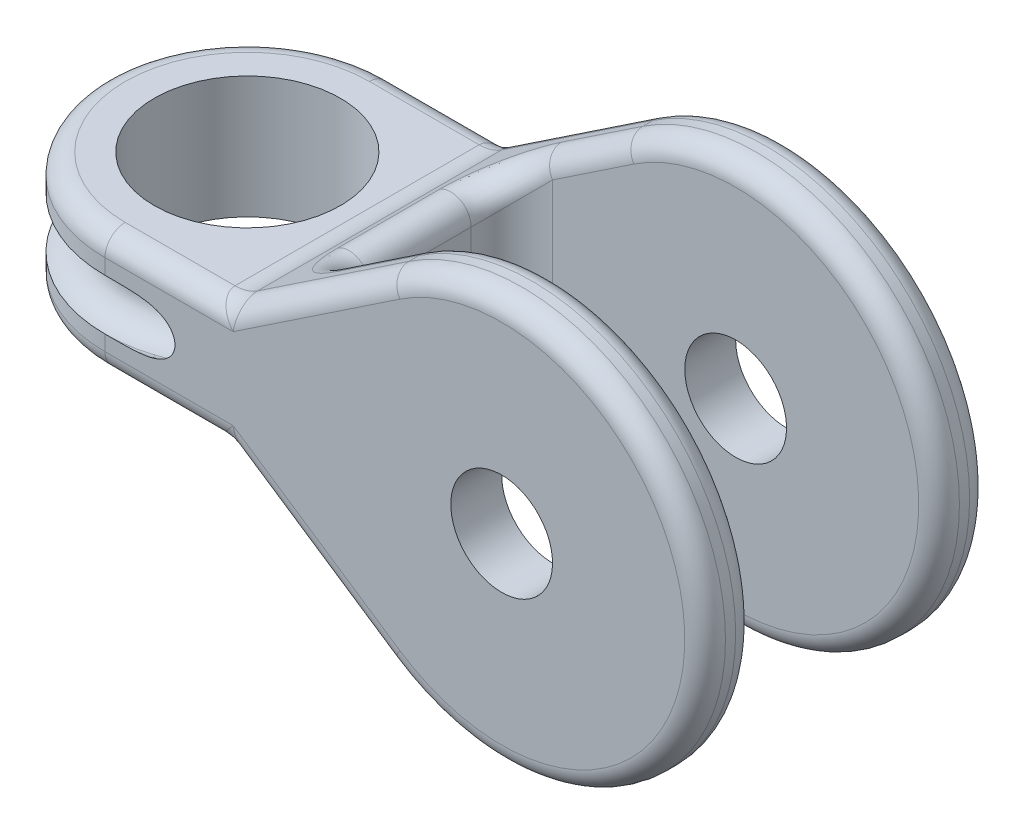
SolidWorks part; units mm, degrees
ref_plane "Front Plane" through (0, 0, 0) normal (0, 0, 1) x (1, 0, 0)
ref_plane "Top Plane" through (0, 0, 0) normal (0, 1, 0) x (1, 0, 0)
ref_plane "Right Plane" through (0, 0, 0) normal (1, 0, 0) x (0, 0, -1)
ref_plane "Front" through (0, 0, 4.5) normal (0, 0, 1) x (1, 0, 0)
ref_plane "Back" through (0, 0, -4.5) normal (0, 0, -1) x (-1, 0, 0)
sketch "Sketch8" plane through (0, 0, 4.5) normal (0, 0, 1) x (1, 0, 0)
  circle A0 centre (0, 0) radius 10
  circle A1 centre (0, 0) radius 2.5
  dimension "D1" = 20
  dimension "D2" = 5
extrude "Boss-Extrude3" add sketch "Sketch8" along normal blind 2.5
sketch "Sketch10" plane through (0, 0, -4.5) normal (0, 0, -1) x (-1, 0, 0)
  circle A0 centre (0, 0) radius 10
  circle A1 centre (0, 0) radius 2.5
  dimension "D1" = 20
  dimension "D2" = 5
extrude "Boss-Extrude4" add sketch "Sketch10" along normal blind 2.5 separate body
sketch "Sketch11" plane through (0, 0, 0) normal (0, 1, 0) x (1, 0, 0)
  line L0 (-38.7738, 0) -> (13.2618, 0) construction
  line L1 (-10, 7) -> (-10, -7) construction
  line L2 (-19.5, -7) -> (-13.5, -7)
  line L4 (-19.5, 7) -> (-13.5, 7)
  line L5 (-13.5, -7) -> (-13.5, 7)
  line L6 (-24.0555, -5.3148) -> (-13.5, 7) construction
  line L7 (-24.0555, 5.3148) -> (-13.5, -7) construction
  line L8 (-10, -7) -> (10, -7) construction
  arc A0 (-19.5, 7) -> (-19.5, -7) centre (-19.5, 0) ccw
  circle A1 centre (-19.5, 0) radius 4.575
  point P17 (-19.5, 0)
  dimension "D1" = 14
  dimension "D2" = 9.15
  dimension "D3" = 3.5
extrude "Boss-Extrude9" add sketch "Sketch11" along normal blind 3 and the other way blind 3 separate body contours L4 L5 L2 A0 | A1
sketch "Sketch12" plane through (0, 0, 0) normal (0, 1, 0) x (1, 0, 0)
  line L0 (-13.5, -7) -> (-10, -7)
  line L1 (-10, -7) -> (-10, 0)
  line L2 (-11, 0) -> (11, 0) construction
  line L3 (-10, 0) -> (-13.5, 0)
  line L4 (-13.5, -7) -> (-13.5, 7) construction
  line L5 (-13.5, 0) -> (-13.5, -7)
  point P0 (-13.5, -7)
  point P1 (-10, -7)
extrude "Boss-Extrude10" add sketch "Sketch12" along normal blind 3 and the other way blind 3
sketch "Sketch22" plane through (0, 0, 7) normal (0, 0, 1) x (1, 0, 0)
  line L0 (-19.5, 3) -> (-10, 3) construction
  line L1 (-10, 0) -> (-14.8775, 0) construction
  line L2 (-10, -3) -> (-10, 3) construction
  line L3 (-13.5, 3) -> (-5.5604, 8.3116)
  line L4 (-13.5, -3) -> (-5.5604, -8.3116)
  line L5 (-13.5, 3) -> (-13.5, -3)
  line L6 (-5.5604, 8.3116) -> (-5.5604, -8.3116)
  circle A0 centre (0, 0) radius 10 construction
  point P0 (-13.5, 3)
  point P9 (-13.5, -3)
  dimension "D1" = 3.5
sketch "Sketch14" plane through (0, 0, 7) normal (0, 0, 1) x (1, 0, 0)
  line L0 (-13.381, 2.0953) -> (-6.2511, 7.8054)
  line L1 (-13.381, -2.0953) -> (-6.2511, -7.8054)
  line L2 (-6.2511, 7.8054) -> (-6.2511, -7.8054)
  line L3 (-13.381, 2.0953) -> (-13.381, -2.0953)
  circle A0 centre (0, 0) radius 10 construction
  circle A1 centre (0, 0) radius 10 construction
  dimension "D1" = 3.5
extrude "Boss-Extrude12" add sketch "Sketch14" against normal through all
extrude "Boss-Extrude14" add sketch "Sketch22" against normal through all
sketch "Sketch16" plane through (0, 0, 0) normal (0, 1, 0) x (1, 0, 0)
  line L0 (-13.5, -7) -> (-13.5, 7) construction
  line L1 (-9, -4.5) -> (-2.7376, -4.5)
  line L2 (11.3013, 0) -> (-30.4765, 0) construction
  line L4 (-11, -2.5) -> (-11, 2.5)
  line L10 (-9, 4.5) -> (-2.7376, 4.5)
  line L11 (-2.7376, -4.5) -> (-2.7376, 4.5)
  line L12 (-11, -4.5) -> (-2.7376, 4.5) construction
  line L13 (-11, 4.5) -> (-2.7376, -4.5) construction
  arc A5 (-9, -4.5) -> (-11, -2.5) centre (-9, -2.5) cw
  arc A6 (-11, 2.5) -> (-9, 4.5) centre (-9, 2.5) cw
  point P2 (-11, 0)
  point P4 (-13.5, 0)
  dimension "D2" = 2
  dimension "D1" = 2.5
extrude "Cut-Extrude3" cut sketch "Sketch16" against normal through all and the other way through all
fillet "Fillet6" radius 1 6 edges at (10, 0, 7) (10, 0, -7) (-9.5302, -5.6558, 7) (-9.5302, 5.6558, 7) (-9.5302, 5.6558, -7) (-9.5302, -5.6558, -7)
sketch "Sketch21" plane through (0, 0, 0) normal (0, 0, 1) x (1, 0, 0)
  line L0 (-27.75, 0) -> (-28.174, 0) construction
  line L1 (-19.5, 6.0919) -> (-19.5, -5.6596) construction
  line L2 (-25.1454, 0) -> (-27.3, 0) construction
  line L3 (-26.5, 3) -> (-26.5, -3) construction
  arc A0 (-26.5, -1.25) -> (-26.5, 1.25) centre (-26.5, 0) ccw
  ellipse E0 centre (-26.5, 0) end of major axis (-26.5, 1.25) minor radius 0.8 (-26.5, 1.25) -> (-26.5, -1.25) ccw
  point P2 (-26.5, 0)
  dimension "D1" = 0.8
  dimension "D2" = 2.5
revolve "Cut-Revolve4" cut sketch "Sketch21" angle 360 about L1
fillet "Fillet7" radius 1 6 edges at (-15.6008, -3, -7) (-26.5, -3, 0) (-15.6008, -3, 7) (-15.6008, 3, -7) (-15.6008, 3, 7) (-26.5, 3, 0)
fillet "Fillet8" radius 2 6 edges at (-13.4111, -2.7071, 6.7071) (-13.4111, -2.7071, -6.7071) (-13.4111, 2.7071, 6.7071) (-13.4111, 2.7071, -6.7071) (-13.5, -3, 0) (-13.5, 3, 0)
fillet "Fillet9" radius 1 12 edges at (-10.4142, 5.0644, -3.9142) (-7.2802, 7.161, -4.5) (10, 0, -4.5) (-7.2802, -7.161, -4.5) (-10.4142, -5.0644, -3.9142) (-11, -4.6725, 0) (-10.4142, -5.0644, 3.9142) (-7.2802, -7.161, 4.5) (10, 0, 4.5) (-7.2802, 7.161, 4.5) (-10.4142, 5.0644, 3.9142) (-11, 4.6725, 0)
